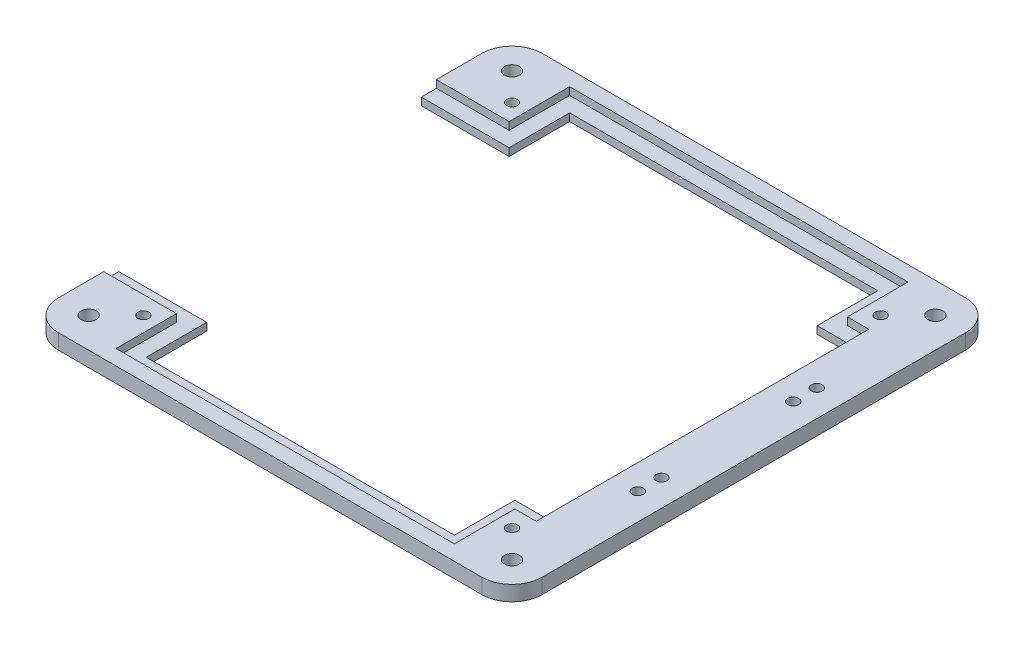
SolidWorks part; units mm, degrees
ref_plane "Front Plane" through (0, 0, 0) normal (0, 0, 1) x (1, 0, 0)
ref_plane "Top Plane" through (0, 0, 0) normal (0, 1, 0) x (1, 0, 0)
ref_plane "Right Plane" through (0, 0, 0) normal (1, 0, 0) x (0, 0, -1)
sketch "Sketch1" plane through (0, 0, 0) normal (0, 1, 0) x (1, 0, 0)
  line L0 (0, 0) -> (0, 25.4)
  line L1 (12.7, 38.1) -> (190.5, 38.1)
  line L2 (203.2, 25.4) -> (203.2, -152.4)
  line L3 (190.5, -165.1) -> (12.7, -165.1)
  line L4 (0, -152.4) -> (0, -127)
  line L5 (0, -127) -> (181.61, -127)
  line L6 (181.61, -127) -> (181.61, 0)
  line L7 (181.61, 0) -> (0, 0)
  arc A0 (12.7, -165.1) -> (0, -152.4) centre (12.7, -152.4) cw
  arc A1 (203.2, -152.4) -> (190.5, -165.1) centre (190.5, -152.4) cw
  arc A2 (190.5, 38.1) -> (203.2, 25.4) centre (190.5, 25.4) cw
  arc A3 (0, 25.4) -> (12.7, 38.1) centre (12.7, 25.4) cw
  point P13 (203.2, -165.1)
  point P16 (203.2, 38.1)
  point P19 (0, 38.1)
  dimension "D6" = 12.7
  dimension "D1" = 203.2
  dimension "D2" = 38.1
  dimension "D3" = 203.2
  dimension "D4" = 181.61
  dimension "D5" = 127
extrude "Boss-Extrude2" add sketch "Sketch1" along normal blind 6.35
sketch "Sketch2" plane through (0, 6.35, 0) normal (0, 1, 0) x (1, 0, 0)
  circle A0 centre (12.7, 25.4) radius 3.175
  circle A1 centre (190.5, 25.4) radius 3.175
  circle A2 centre (190.5, -152.4) radius 3.175
  circle A3 centre (12.7, -152.4) radius 3.175
  arc A4 (12.7, 38.1) -> (0, 25.4) centre (12.7, 25.4) ccw construction
  dimension "D1" = 6.35
extrude "Cut-Extrude1" cut sketch "Sketch2" against normal through all
sketch "Sketch7" plane through (0, 6.35, 0) normal (0, 1, 0) x (1, 0, 0)
  line L0 (192.024, -28.194) -> (192.024, -33.528) construction
  line L1 (192.024, -38.1) -> (192.024, -88.9) construction
  line L2 (192.024, -93.472) -> (192.024, -98.806) construction
  line L3 (192.024, -23.622) -> (192.024, 38.1) construction
  line L4 (190.5, 38.1) -> (12.7, 38.1) construction
  line L5 (192.024, -103.378) -> (192.024, -165.1) construction
  line L6 (12.7, -165.1) -> (190.5, -165.1) construction
  line L7 (189.738, -25.908) -> (181.61, -25.908) construction
  line L8 (181.61, 0) -> (181.61, -127) construction
  circle A0 centre (192.024, -101.092) radius 2.286
  circle A1 centre (192.024, -91.186) radius 2.286
  circle A2 centre (192.024, -35.814) radius 2.286
  circle A3 centre (192.024, -25.908) radius 2.286
  dimension "D1" = 4.572
  dimension "D2" = 5.334
  dimension "D3" = 5.334
  dimension "D4" = 50.8
  dimension "D5" = 8.128
extrude "Cut-Extrude3" cut sketch "Sketch7" against normal blind 12.7
sketch "Sketch8" plane through (0, 0, 0) normal (0, -1, 0) x (-1, 0, 0)
  line L0 (-3.7197, -161.3803) -> (-199.4803, 34.3803) construction
  line L1 (-24.1978, 13.9022) -> (-24.1978, 38.1) construction
  line L2 (-190.5, 38.1) -> (-12.7, 38.1) construction
  line L3 (-24.1978, 13.9022) -> (0, 13.9022) construction
  line L5 (-24.1978, 13.9022) -> (-3.7197, 34.3803) construction
  line L6 (0, 25.4) -> (0, 0) construction
  arc A0 (0, 25.4) -> (-12.7, 38.1) centre (-12.7, 25.4) ccw construction
  circle A1 centre (-24.1978, 13.9022) radius 2.286
  arc A2 (-12.7, -165.1) -> (0, -152.4) centre (-12.7, -152.4) ccw construction
  arc A3 (-190.5, 38.1) -> (-203.2, 25.4) centre (-190.5, 25.4) ccw construction
  circle A4 centre (-24.1978, -140.9022) radius 2.286
  circle A5 centre (-179.0022, -140.9022) radius 2.286
  circle A6 centre (-179.0022, 13.9022) radius 2.286
  point P8 (-101.6, -63.5)
  dimension "D2" = 4.572
  dimension "D1" = 28.9603
  dimension "D3" = 4
extrude "Cut-Extrude4" cut sketch "Sketch8" against normal through all
sketch "Sketch9" plane through (0, 6.35, 0) normal (0, 1, 0) x (1, 0, 0)
  line L0 (0, 0) -> (181.61, 0) construction
  line L1 (36.8978, 0) -> (166.3022, 0)
  line L2 (36.8978, 0) -> (36.8978, 25.4)
  line L3 (36.8978, 25.4) -> (166.3022, 25.4)
  line L4 (166.3022, 0) -> (166.3022, 25.4)
  line L5 (181.61, -127) -> (0, -127) construction
  line L6 (166.3022, -127) -> (36.8978, -127)
  line L7 (166.3022, -127) -> (166.3022, -152.4)
  line L8 (166.3022, -152.4) -> (36.8978, -152.4)
  line L9 (36.8978, -127) -> (36.8978, -152.4)
  line L10 (12.7, -165.1) -> (190.5, -165.1) construction
  line L11 (190.5, 38.1) -> (12.7, 38.1) construction
  circle A0 centre (179.0022, 13.9022) radius 2.286 construction
  circle A1 centre (24.1978, 13.9022) radius 2.286 construction
  point P12 (101.6, -152.4)
  point P15 (101.6, -165.1)
  dimension "D1" = 12.7
  dimension "D2" = 12.7
  dimension "D3" = 12.7
extrude "Cut-Extrude5" cut sketch "Sketch9" against normal through all
sketch "Sketch10" plane through (0, 6.35, 0) normal (0, 1, 0) x (1, 0, 0)
  line L0 (0, 6.35) -> (30.5478, 6.35)
  line L1 (0, 25.4) -> (0, 0) construction
  line L2 (30.5478, 6.35) -> (30.5478, 31.75)
  line L3 (30.5478, 31.75) -> (172.6522, 31.75)
  line L4 (172.6522, 31.75) -> (172.6522, 6.35)
  line L5 (172.6522, 6.35) -> (181.61, 6.35)
  line L6 (181.61, 6.35) -> (181.61, 0)
  line L7 (166.3022, 0) -> (181.61, 0) construction
  line L8 (181.61, 0) -> (181.61, -127) construction
  line L9 (181.61, 0) -> (166.3022, 0)
  line L10 (166.3022, 0) -> (166.3022, 25.4)
  line L11 (166.3022, 25.4) -> (36.8978, 25.4)
  line L12 (36.8978, 25.4) -> (36.8978, 0)
  line L13 (36.8978, 0) -> (0, 0)
  line L14 (0, 0) -> (0, 6.35)
  line L15 (-796.8, -63.5) -> (49203.2, -63.5) construction
  line L16 (203.2, -152.4) -> (203.2, 25.4) construction
  line L17 (0, -127) -> (0, -133.35)
  line L18 (36.8978, -127) -> (0, -127)
  line L19 (36.8978, -152.4) -> (36.8978, -127)
  line L20 (166.3022, -152.4) -> (36.8978, -152.4)
  line L21 (166.3022, -127) -> (166.3022, -152.4)
  line L22 (181.61, -127) -> (166.3022, -127)
  line L23 (181.61, -133.35) -> (181.61, -127)
  line L24 (172.6522, -133.35) -> (181.61, -133.35)
  line L25 (172.6522, -158.75) -> (172.6522, -133.35)
  line L26 (30.5478, -158.75) -> (172.6522, -158.75)
  line L27 (30.5478, -133.35) -> (30.5478, -158.75)
  line L28 (0, -133.35) -> (30.5478, -133.35)
  point P28 (203.2, -63.5)
  dimension "D1" = 6.35
  dimension "D2" = 6.35
  dimension "D3" = 6.35
  dimension "D4" = 6.35
  dimension "D5" = 6.35
extrude "Cut-Extrude6" cut sketch "Sketch10" against normal blind 3.175
